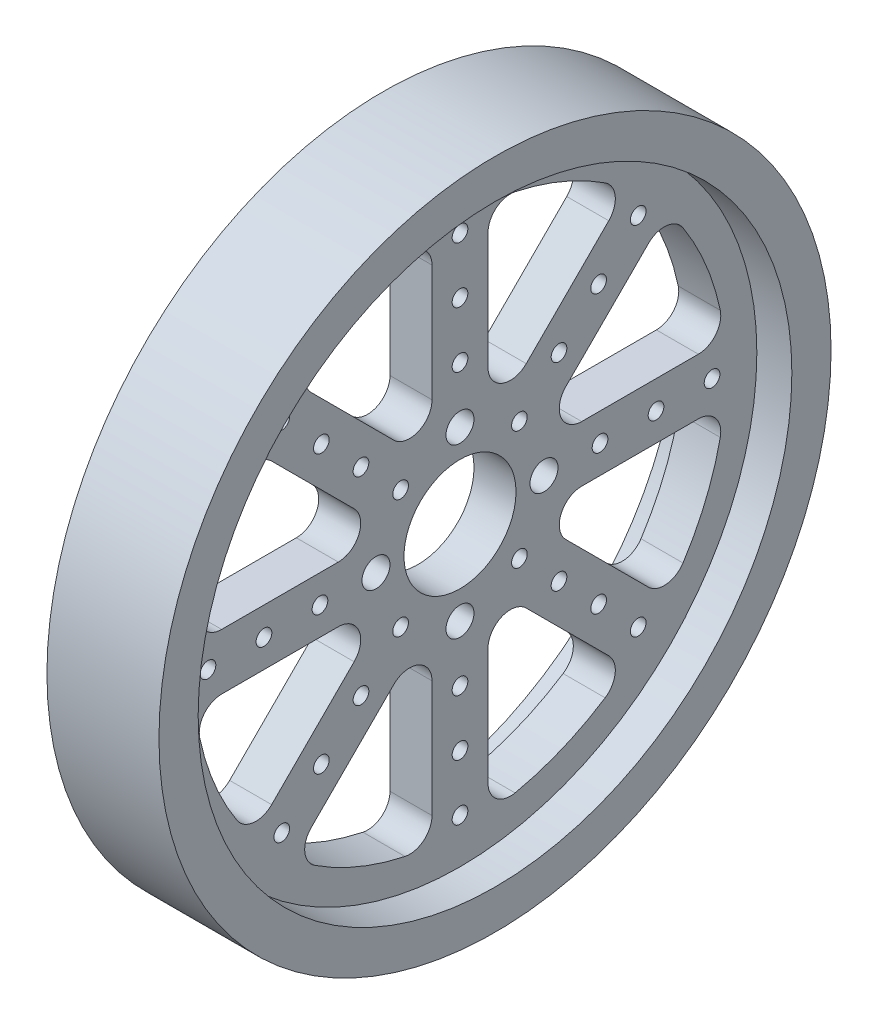
SolidWorks part; units mm, degrees
material "ﾎﾟﾘｳﾚﾀﾝ(POLYURETHANE) (11671)"
ref_plane "正面" through (0, 0, 0) normal (0, 0, 1) x (1, 0, 0)
ref_plane "平面" through (0, 0, 0) normal (0, 1, 0) x (1, 0, 0)
ref_plane "右側面" through (0, 0, 0) normal (1, 0, 0) x (0, 0, -1)
sketch "ｽｹｯﾁ1" plane through (0, 0, 0) normal (1, 0, 0) x (0, 0, -1)
  circle A0 centre (0, 0) radius 67.31
  dimension "D1" = 134.62
extrude "ﾎﾞｽ - 押し出し1" add sketch "ｽｹｯﾁ1" along normal mid plane 9.525
sketch "ｽｹｯﾁ2" plane through (4.7625, 0, 0) normal (1, 0, 0) x (0, 0, -1)
  line L0 (0, 0) -> (0, 19.05) construction
  line L1 (0, 0) -> (0, 67.31) construction
  line L2 (0, 0) -> (67.31, 0) construction
  line L3 (43.1052, 52.0855) -> (-4.4901, 4.4901)
  line L4 (-6.35, 67.31) -> (6.35, 67.31)
  line L5 (-6.35, 67.31) -> (-6.35, 0)
  line L6 (-6.35, 0) -> (6.35, 0)
  line L7 (6.35, 67.31) -> (6.35, 0)
  line L8 (-6.35, 67.31) -> (6.35, 0) construction
  line L9 (-6.35, 0) -> (6.35, 67.31) construction
  line L10 (52.0855, 43.1052) -> (4.4901, -4.4901)
  line L11 (67.31, 6.35) -> (0, 6.35)
  line L12 (67.31, -6.35) -> (0, -6.35)
  line L13 (52.0855, -43.1052) -> (4.4901, 4.4901)
  line L14 (43.1052, -52.0855) -> (-4.4901, -4.4901)
  line L15 (6.35, -67.31) -> (6.35, 0)
  line L16 (-6.35, -67.31) -> (-6.35, 0)
  line L17 (-43.1052, -52.0855) -> (4.4901, -4.4901)
  line L18 (-52.0855, -43.1052) -> (-4.4901, 4.4901)
  line L19 (-67.31, -6.35) -> (0, -6.35)
  line L20 (-67.31, 6.35) -> (0, 6.35)
  line L21 (-52.0855, 43.1052) -> (-4.4901, -4.4901)
  line L22 (-43.1052, 52.0855) -> (4.4901, 4.4901)
  line L23 (0, 0) -> (40.4112, 40.4112) construction
  circle A0 centre (0, 0) radius 12.7
  circle A1 centre (0, 19.05) radius 3.175
  circle A2 centre (19.05, 0) radius 3.175
  circle A3 centre (0, -19.05) radius 3.175
  circle A4 centre (-19.05, 0) radius 3.175
  circle A5 centre (0, 0) radius 19.05 construction
  circle A6 centre (0, 0) radius 67.31 construction
  circle A7 centre (0, 31.75) radius 1.778
  circle A8 centre (0, 44.45) radius 1.778
  circle A9 centre (0, 57.15) radius 1.778
  circle A10 centre (0, -57.15) radius 1.778
  circle A11 centre (0, -44.45) radius 1.778
  circle A12 centre (0, -31.75) radius 1.778
  circle A13 centre (-40.4112, -40.4112) radius 1.778
  circle A14 centre (-31.4309, -31.4309) radius 1.778
  circle A15 centre (-22.4506, -22.4506) radius 1.778
  circle A16 centre (22.4506, 22.4506) radius 1.778
  circle A17 centre (31.4309, 31.4309) radius 1.778
  circle A18 centre (40.4112, 40.4112) radius 1.778
  circle A19 centre (-57.15, 0) radius 1.778
  circle A20 centre (-44.45, 0) radius 1.778
  circle A21 centre (-31.75, 0) radius 1.778
  circle A22 centre (31.75, 0) radius 1.778
  circle A23 centre (44.45, 0) radius 1.778
  circle A24 centre (57.15, 0) radius 1.778
  circle A25 centre (-40.4112, 40.4112) radius 1.778
  circle A26 centre (-31.4309, 31.4309) radius 1.778
  circle A27 centre (-22.4506, 22.4506) radius 1.778
  circle A28 centre (22.4506, -22.4506) radius 1.778
  circle A29 centre (31.4309, -31.4309) radius 1.778
  circle A30 centre (40.4112, -40.4112) radius 1.778
  circle A31 centre (0, 57.15) radius 1.778
  circle A32 centre (0, 44.45) radius 1.778
  circle A33 centre (0, 31.75) radius 1.778
  circle A34 centre (0, -31.75) radius 1.778
  circle A35 centre (0, -44.45) radius 1.778
  circle A36 centre (0, -57.15) radius 1.778
  circle A37 centre (40.4112, 40.4112) radius 1.778
  circle A38 centre (31.4309, 31.4309) radius 1.778
  circle A39 centre (22.4506, 22.4506) radius 1.778
  circle A40 centre (-22.4506, -22.4506) radius 1.778
  circle A41 centre (-31.4309, -31.4309) radius 1.778
  circle A42 centre (-40.4112, -40.4112) radius 1.778
  circle A43 centre (57.15, 0) radius 1.778
  circle A44 centre (44.45, 0) radius 1.778
  circle A45 centre (31.75, 0) radius 1.778
  circle A46 centre (-31.75, 0) radius 1.778
  circle A47 centre (-44.45, 0) radius 1.778
  circle A48 centre (-57.15, 0) radius 1.778
  circle A49 centre (40.4112, -40.4112) radius 1.778
  circle A50 centre (31.4309, -31.4309) radius 1.778
  circle A51 centre (22.4506, -22.4506) radius 1.778
  circle A52 centre (-22.4506, 22.4506) radius 1.778
  circle A53 centre (-31.4309, 31.4309) radius 1.778
  circle A54 centre (-40.4112, 40.4112) radius 1.778
  circle A55 centre (0, 0) radius 57.15 construction
  circle A56 centre (0, 0) radius 60.325
  circle A57 centre (13.4704, 13.4704) radius 1.778
  circle A58 centre (13.4704, -13.4704) radius 1.778
  circle A59 centre (-13.4704, -13.4704) radius 1.778
  circle A60 centre (-13.4704, 13.4704) radius 1.778
  point P47 (0, 33.655)
  dimension "D1" = 25.4
  dimension "D2" = 6.35
  dimension "D5" = 3.556
  dimension "D10" = 12.7
  dimension "D12" = 120.65
  dimension "D13" = 4
  dimension "D3" = 19.05
  dimension "D6" = 63.5
  dimension "D7" = 88.9
  dimension "D8" = 114.3
  dimension "D11" = 8
  dimension "D4" = 4
  dimension "D9" = 8
extrude "ｶｯﾄ - 押し出し1" cut sketch "ｽｹｯﾁ2" against normal through all contours L21 A56 L20 | L19 A56 L18 | L17 A56 L16 | L15 A56 L14 | L13 A56 L12 | L11 A56 L10 | L3 A56 L7 | L5 A56 L22 | A25 | A26 | A27 | A1 | A7 | A8 | L15 A0 L12 | L12 A0 L13 L10 L15 | L13 A0 L10 | L10 A0 L11 L7 L13 | L15 L10 L13 L7 | L22 L11 L20 L3 L18 L5 L6 L7 L13 | L16 L21 L14 L19 L12 L17 L10 L15 L6 | L16 A0 L17 L14 L19 | L17 A0 L14 | L14 A0 L15 L12 L17 | L19 L14 L17 L12 | L17 L12 L15 L10 | L21 L16 L19 L14 | L19 A0 L16 | L18 A0 L19 L16 L21 | L20 A0 L21 L18 L5 | L5 A0 L20 | L11 A0 L7 | L11 L22 L13 L7 | L20 L5 L18 L3 | L21 A0 L18 | L18 L21 L16 L5 | L22 A0 L5 L20 L3 | L7 A0 L3 L22 L11 | L22 L3 L20 L11 | L3 A0 L22 | A9 | A16 | A18 | A2 | A22 | A23 | A24 | A17 | A28 | A29 | A30 | A3 | A11 | A12 | A15 | A14 | A13 | A10 | A19 | A20 | A4 | A21 | A21 | A20 | A19 | A59 | A15 | A12 | A58 | A60 | A14 | A13 | A11 | A10 | A28 | A29 | A30 | A22 | A23 | A24 | A57 | A16 | A17 | A18 | A7 | A8 | A9 | A25 | A26 region at (4.7625, 41.7545, -17.2953) region at (4.7625, 17.2953, -41.7545) region at (4.7625, 9.0413, -3.745) region at (4.7625, 11.3616, 0) region at (4.7625, 8.0339, -8.0339) region at (4.7625, 41.7545, 17.2953) region at (4.7625, 7.2268, 0) region at (4.7625, 9.0413, 3.745) region at (4.7625, 3.745, -9.0413) region at (4.7625, 5.1101, -5.1101) region at (4.7625, 0, -11.3616) region at (4.7625, 2.7742, 0) region at (4.7625, 5.1101, 5.1101) region at (4.7625, 8.0339, 8.0339) region at (4.7625, 0, -7.2268) region at (4.7625, -3.745, -9.0413) region at (4.7625, -17.2953, -41.7545) region at (4.7625, 17.2953, 41.7545) region at (4.7625, 3.745, 9.0413) region at (4.7625, -2.7742, 0) region at (4.7625, -5.1101, -5.1101) region at (4.7625, 0, 7.2268) region at (4.7625, 0, 11.3616) region at (4.7625, -9.0413, -3.745) region at (4.7625, -8.0339, -8.0339) region at (4.7625, -41.7545, -17.2953) region at (4.7625, -17.2953, 41.7545) region at (4.7625, -3.745, 9.0413) region at (4.7625, -5.1101, 5.1101) region at (4.7625, -7.2268, 0) region at (4.7625, -8.0339, 8.0339) region at (4.7625, -9.0413, 3.745) region at (4.7625, -11.3616, 0) region at (4.7625, -41.7545, 17.2953) region at (4.7625, 19.05, 0) region at (4.7625, 0, -19.05) region at (4.7625, -19.05, 0) region at (4.7625, 0, 19.05) region at (4.7625, 31.75, 0) region at (4.7625, 44.45, 0) region at (4.7625, 57.15, 0) region at (4.7625, -57.15, 0) region at (4.7625, -44.45, 0) region at (4.7625, -31.75, 0) region at (4.7625, -40.4112, 40.4112) region at (4.7625, -31.4309, 31.4309) region at (4.7625, -22.4506, 22.4506) region at (4.7625, 22.4506, -22.4506) region at (4.7625, 31.4309, -31.4309) region at (4.7625, 40.4112, -40.4112) region at (4.7625, 0, 57.15) region at (4.7625, 0, 44.45) region at (4.7625, 0, 31.75) region at (4.7625, 0, -31.75) region at (4.7625, 0, -44.45) region at (4.7625, 0, -57.15) region at (4.7625, 40.4112, 40.4112) region at (4.7625, 31.4309, 31.4309) region at (4.7625, 22.4506, 22.4506) region at (4.7625, -22.4506, -22.4506)
fillet "ﾌｨﾚｯﾄ1" radius 5.08 24 edges at (0, 59.9899, -6.35) (0, 15.3303, -6.35) (0, 46.9094, -37.9291) (0, 6.35, 59.9899) (0, -37.9291, 46.9094) (0, -46.9094, 37.9291) (0, -6.35, 59.9899) (0, 37.9291, 46.9094) (0, 6.35, 15.3303) (0, -6.35, 15.3303) (0, -15.3303, 6.35) (0, -59.9899, 6.35) (0, -46.9094, -37.9291) (0, -59.9899, -6.35) (0, -15.3303, -6.35) (0, 6.35, -15.3303) (0, -6.35, -15.3303) (0, -37.9291, -46.9094) (0, 6.35, -59.9899) (0, 37.9291, -46.9094) (0, -6.35, -59.9899) (0, 59.9899, 6.35) (0, 46.9094, 37.9291) (0, 15.3303, 6.35)
ref_axis "軸1" through (-4.7625, 0, 0) along (1, 0, 0)
sketch "ｽｹｯﾁ3" plane through (0, 0, 0) normal (1, 0, 0) x (0, 0, -1)
  circle A0 centre (0, 0) radius 76.2
  circle A2 centre (0, 0) radius 67.31
  circle A3 centre (0, 0) radius 67.31
  dimension "D1" = 152.4
  dimension "D2" = 0
extrude "ﾎﾞｽ - 押し出し2" add sketch "ｽｹｯﾁ3" along normal mid plane 25.4
